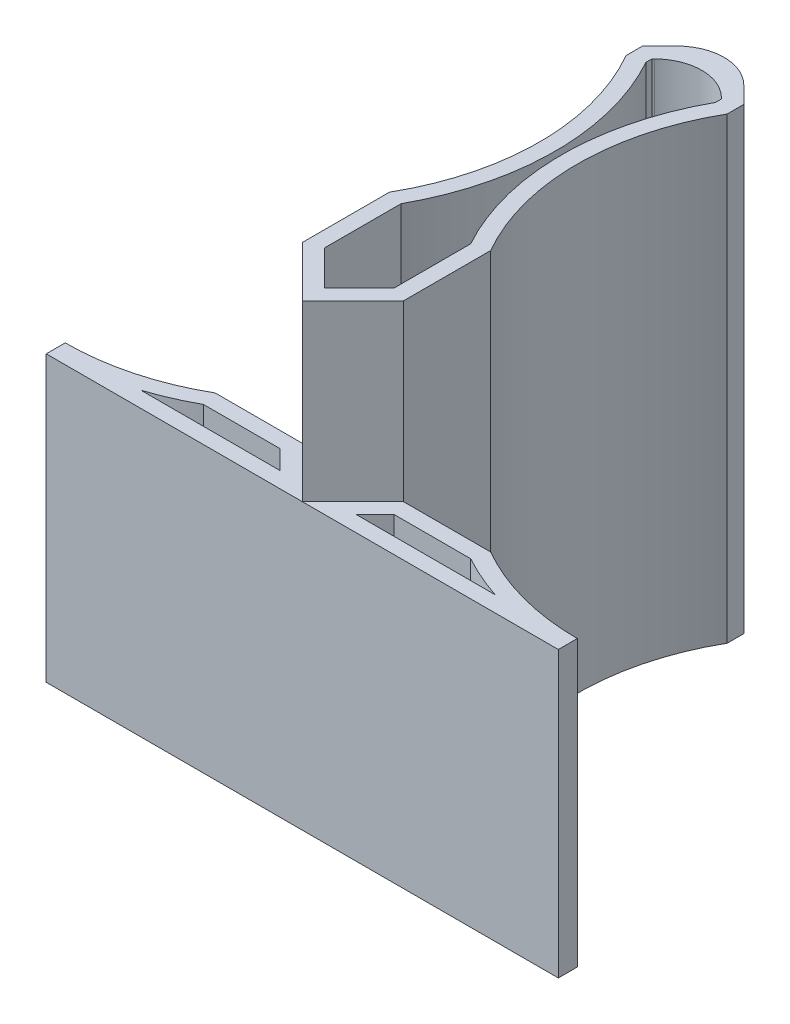
SolidWorks part; units mm, degrees
ref_plane "Front Plane" through (0, 0, 0) normal (0, 0, 1) x (1, 0, 0)
ref_plane "Top Plane" through (0, 0, 0) normal (0, 1, 0) x (1, 0, 0)
ref_plane "Right Plane" through (0, 0, 0) normal (1, 0, 0) x (0, 0, -1)
sketch "Sketch1" plane through (0, 0, 0) normal (0, 1, 0) x (1, 0, 0)
  line L0 (23.7595, 41.275) -> (41.275, 41.275) construction
  line L1 (-41.275, -41.275) -> (-23.7595, -41.275) construction
  line L2 (-41.275, -41.275) -> (-41.275, -23.7595) construction
  line L3 (-41.275, 41.275) -> (-23.7595, 41.275) construction
  line L4 (41.275, -41.275) -> (41.275, -23.7595) construction
  line L5 (-41.275, -41.275) -> (41.275, 41.275) construction
  line L6 (-41.275, 41.275) -> (41.275, -41.275) construction
  line L7 (41.275, 23.7595) -> (41.275, 41.275) construction
  line L8 (-41.275, 23.7595) -> (-41.275, 41.275) construction
  line L9 (23.7595, -41.275) -> (41.275, -41.275) construction
  line L10 (24.7569, 45.085) -> (45.085, 45.085) construction
  line L11 (45.085, 24.7569) -> (45.085, 45.085) construction
  line L12 (45.085, -45.085) -> (45.085, -24.7569) construction
  line L13 (24.7569, -45.085) -> (45.085, -45.085) construction
  line L14 (-45.085, -45.085) -> (-24.7569, -45.085) construction
  line L15 (-45.085, -45.085) -> (-45.085, -24.7569) construction
  line L16 (-45.085, 24.7569) -> (-45.085, 45.085) construction
  line L17 (-45.085, 45.085) -> (-24.7569, 45.085) construction
  line L19 (-51.435, -51.435) -> (51.435, -51.435) construction
  line L20 (-51.435, -51.435) -> (-51.435, 51.435) construction
  line L21 (-51.435, 51.435) -> (51.435, 51.435) construction
  line L22 (51.435, -51.435) -> (51.435, 51.435) construction
  line L23 (-51.435, -51.435) -> (51.435, 51.435) construction
  line L24 (-51.435, 51.435) -> (51.435, -51.435) construction
  arc A1 (-41.275, 23.7595) -> (-41.275, -23.7595) centre (0, 0) ccw construction
  arc A2 (23.7595, 41.275) -> (-23.7595, 41.275) centre (0, 0) ccw construction
  arc A3 (-23.7595, -41.275) -> (23.7595, -41.275) centre (0, 0) ccw construction
  arc A4 (41.275, -23.7595) -> (41.275, 23.7595) centre (0, 0) ccw construction
  arc A5 (45.085, -24.7569) -> (45.085, 24.7569) centre (0, 0) ccw construction
  arc A6 (-24.7569, -45.085) -> (24.7569, -45.085) centre (0, 0) ccw construction
  arc A7 (-45.085, 24.7569) -> (-45.085, -24.7569) centre (0, 0) ccw construction
  arc A8 (24.7569, 45.085) -> (-24.7569, 45.085) centre (0, 0) ccw construction
  point P0 (0, 0)
  dimension "D1" = 82.55
  dimension "D2" = 82.55
  dimension "D3" = 95.25
  dimension "D4" = 3.81
sketch "Sketch2" plane through (0, 0, 0) normal (0, 0, 1) x (1, 0, 0)
  line L0 (0, 48) -> (0, 0) construction
  line L1 (0, 0) -> (0, -9.15) construction
  line L2 (0, 48) -> (0, 82.925) construction
  dimension "Cage height" = 48
  dimension "Plate height" = 34.925
  dimension "D1" = 57.15
  dimension "D2" = 9.15
sketch "Sketch13" plane through (0, 0, 0) normal (0, 1, 0) x (1, 0, 0)
  line L0 (-51.435, -51.435) -> (51.435, -51.435) construction
  line L1 (-41.275, -41.275) -> (-23.7595, -41.275) construction
  line L2 (-41.275, -41.275) -> (-41.275, -23.7595) construction
  line L4 (-51.435, -51.435) -> (0, -51.435)
  line L5 (-41.275, -41.275) -> (-23.7595, -41.275)
  line L6 (-41.275, -41.275) -> (-41.275, -23.7595)
  line L9 (0, -47.625) -> (0, -51.435)
  line L10 (-51.435, 51.435) -> (51.435, -51.435) construction
  line L11 (-41.275, 23.7595) -> (-41.275, 41.275) construction
  line L12 (-51.435, -51.435) -> (-51.435, 51.435) construction
  line L13 (-51.435, 51.435) -> (-41.275, 41.275)
  line L14 (-41.275, 23.7595) -> (-41.275, 41.275)
  line L15 (-51.435, -51.435) -> (-51.435, 51.435)
  arc A0 (-23.7595, -41.275) -> (23.7595, -41.275) centre (0, 0) ccw construction
  arc A2 (-23.7595, -41.275) -> (0, -47.625) centre (0, 0) ccw
  arc A4 (-41.275, 23.7595) -> (-41.275, -23.7595) centre (0, 0) ccw construction
  arc A5 (-41.275, 23.7595) -> (-41.275, -23.7595) centre (0, 0) ccw
extrude "Boss-Extrude2" add sketch "Sketch13" along normal up to vertex (82.925 mm away) and the other way up to vertex (9.15 mm away) up to point (0, 82.925, 0) other way up to point (0, -9.15, 0)
sketch "Sketch15" plane through (0, 82.925, 0) normal (0, 1, 0) x (1, 0, 0)
  line L0 (0, 0) -> (-51.435, -51.435)
  line L1 (-51.435, -51.435) -> (0, -51.435)
  line L2 (0, -51.435) -> (0, 0)
  line L3 (-51.435, -51.435) -> (51.435, -51.435) construction
extrude "Cut-Extrude2" cut sketch "Sketch15" against normal up to vertex (34.925 mm away) up to point (0, 48, 0)
mirror "Mirror1" about plane through (-51.435, 82.925, 51.435) normal (1, 0, 0) of "Boss-Extrude2", "Cut-Extrude2"
sketch "Sketch16" plane through (0, -9.15, 0) normal (0, -1, 0) x (1, 0, 0)
  line L1 (-51.435, -51.435) -> (51.435, -51.435) construction
  circle A5 centre (-51.435, -13.335) radius 1.35
  dimension "D1" = 2.7
  dimension "D2" = 38.1
extrude "Cut-Extrude3" cut sketch "Sketch16" against normal blind 31.75
sketch "Sketch17" plane through (0, 82.925, 0) normal (0, 1, 0) x (1, 0, 0)
  line L0 (7.0944, 7.0944) -> (-7.0944, -7.0944)
  line L1 (7.0944, 7.0944) -> (-44.3406, 58.5294)
  line L2 (-7.0944, -7.0944) -> (-51.435, 37.2462)
  line L3 (-44.3406, 58.5294) -> (-51.435, 51.435)
  line L4 (-41.275, -41.275) -> (41.275, 41.275) construction
  line L5 (-61.595, 41.275) -> (-51.435, 51.435) construction
  line L6 (-51.435, -51.435) -> (-51.435, 51.435) construction
  line L7 (-51.435, 7.7321) -> (-51.435, 82.5591) construction
  line L8 (-95.7756, -7.0944) -> (-51.435, 37.2462)
  line L9 (-58.5294, 58.5294) -> (-51.435, 51.435)
  line L10 (-109.9644, 7.0944) -> (-58.5294, 58.5294)
  line L11 (-109.9644, 7.0944) -> (-95.7756, -7.0944)
  dimension "D1" = 20.066
extrude "Cut-Extrude4" cut sketch "Sketch17" against normal through all
sketch "Sketch18" plane through (0, 82.925, 0) normal (0, 1, 0) x (1, 0, 0)
  line L19 (-58.42, -24.5934) -> (-58.42, -39.9599)
  line L20 (-58.42, -39.9599) -> (-51.435, -46.9449)
  line L21 (-51.435, -46.9449) -> (-44.45, -39.9599)
  line L22 (-44.45, -39.9599) -> (-44.45, -24.5934)
  line L27 (-58.42, -24.5934) -> (-58.42, -39.9599)
  line L28 (-58.42, -39.9599) -> (-51.435, -46.9449)
  line L29 (-51.435, -46.9449) -> (-44.45, -39.9599)
  line L30 (-44.45, -39.9599) -> (-44.45, -24.5934)
  line L32 (-62.9101, -44.45) -> (-78.2766, -44.45)
  line L33 (-87.0077, -48.26) -> (-59.1001, -48.26)
  line L34 (-59.1001, -48.26) -> (-62.9101, -44.45)
  line L35 (-62.9101, -44.45) -> (-78.2766, -44.45)
  line L36 (-87.0077, -48.26) -> (-59.1001, -48.26)
  line L37 (-59.1001, -48.26) -> (-62.9101, -44.45)
  line L42 (-24.5934, -44.45) -> (-39.9599, -44.45)
  line L43 (-39.9599, -44.45) -> (-43.7699, -48.26)
  line L44 (-43.7699, -48.26) -> (-15.8623, -48.26)
  line L45 (-24.5934, -44.45) -> (-39.9599, -44.45)
  line L46 (-39.9599, -44.45) -> (-43.7699, -48.26)
  line L47 (-43.7699, -48.26) -> (-15.8623, -48.26)
  line L48 (-44.45, 25.7711) -> (-51.435, 32.7561)
  line L49 (-44.45, 25.7711) -> (-51.435, 32.7561)
  line L50 (-51.435, 32.7561) -> (-58.42, 25.7711)
  line L51 (-51.435, 32.7561) -> (-58.42, 25.7711)
  line L52 (-58.42, 25.7711) -> (-58.42, 24.5934)
  line L53 (-58.42, 25.7711) -> (-58.42, 24.5934)
  line L54 (-44.45, 24.5934) -> (-44.45, 25.7711)
  line L55 (-44.45, 24.5934) -> (-44.45, 25.7711)
  arc A5 (-87.0077, -48.26) -> (-78.2766, -44.45) centre (-102.87, 0) ccw
  arc A7 (-58.42, -24.5934) -> (-58.42, 24.5934) centre (-102.87, 0) ccw
  arc A8 (-44.45, 24.5934) -> (-44.45, -24.5934) centre (0, 0) ccw
  arc A10 (-58.42, -24.5934) -> (-58.42, 24.5934) centre (-102.87, 0) ccw
  arc A11 (-44.45, 24.5934) -> (-44.45, -24.5934) centre (0, 0) ccw
  arc A12 (-87.0077, -48.26) -> (-78.2766, -44.45) centre (-102.87, 0) ccw
  arc A14 (-24.5934, -44.45) -> (-15.8623, -48.26) centre (0, 0) ccw
  arc A15 (-24.5934, -44.45) -> (-15.8623, -48.26) centre (0, 0) ccw
  dimension "D1" = 3.175
  dimension "D2" = 3.175
  dimension "D3" = 3.175
extrude "Cut-Extrude5" cut sketch "Sketch18" against normal up to surface (60.325 mm away) contours A11 L55 L49 L51 L53 A10 L27 L28 L29 L30 region at (-51.435, 82.925, 12.1349) up to face at (-51.435, 22.6, -14.685)
sketch "Sketch22" plane through (0, 0, 0) normal (0, 1, 0) x (1, 0, 0)
  line L0 (-51.435, -51.435) -> (-51.435, 51.435) construction
  line L1 (-51.435, 51.435) -> (51.435, 51.435) construction
  circle A0 centre (-51.435, -12.065) radius 1.85
  dimension "D1" = 3.7
  dimension "D2" = 63.5
extrude "Cut-Extrude7" cut sketch "Sketch22" against normal through all both and the other way through all
sketch "Sketch20" plane through (0, 22.6, 0) normal (0, 1, 0) x (1, 0, 0)
  line L7 (-56.039, 19.685) -> (-46.831, 19.685)
  line L9 (-47.3448, -18.415) -> (-55.5252, -18.415)
  line L24 (-44.45, 24.5934) -> (-44.45, 25.7711)
  line L25 (-44.45, 25.7711) -> (-51.435, 32.7561)
  line L26 (-51.435, 32.7561) -> (-58.42, 25.7711)
  line L27 (-58.42, 25.7711) -> (-58.42, 24.5934)
  line L28 (-58.42, -24.5934) -> (-58.42, -39.9599)
  line L29 (-58.42, -39.9599) -> (-51.435, -46.9449)
  line L30 (-51.435, -46.9449) -> (-44.45, -39.9599)
  line L31 (-44.45, -39.9599) -> (-44.45, -24.5934)
  line L32 (-44.45, 24.5934) -> (-44.45, 25.7711)
  line L33 (-44.45, 25.7711) -> (-51.435, 32.7561)
  line L34 (-51.435, 32.7561) -> (-58.42, 25.7711)
  line L35 (-58.42, 25.7711) -> (-58.42, 24.5934)
  line L36 (-58.42, -24.5934) -> (-58.42, -39.9599)
  line L37 (-58.42, -39.9599) -> (-51.435, -46.9449)
  line L38 (-51.435, -46.9449) -> (-44.45, -39.9599)
  line L39 (-44.45, -39.9599) -> (-44.45, -24.5934)
  arc A0 (-58.42, -24.5934) -> (-58.42, 24.5934) centre (-102.87, 0) ccw construction
  arc A1 (-47.3448, -18.415) -> (-44.45, -24.5934) centre (0, 0) ccw
  arc A5 (-58.42, -24.5934) -> (-58.42, 24.5934) centre (-102.87, 0) ccw construction
  arc A9 (-44.45, 24.5934) -> (-44.45, -24.5934) centre (0, 0) ccw construction
  arc A11 (-44.45, 24.5934) -> (-44.45, -24.5934) centre (0, 0) ccw construction
  arc A13 (-58.42, -24.5934) -> (-58.42, 24.5934) centre (-102.87, 0) ccw
  arc A14 (-44.45, 24.5934) -> (-44.45, -24.5934) centre (0, 0) ccw
  arc A15 (-58.42, -24.5934) -> (-55.5252, -18.415) centre (-102.87, 0) ccw
  arc A16 (-44.45, 24.5934) -> (-46.831, 19.685) centre (0, 0) ccw
  arc A18 (-56.039, 19.685) -> (-58.42, 24.5934) centre (-102.87, 0) ccw
  circle A19 centre (-51.435, 13.335) radius 1.35 construction
  circle A20 centre (-51.435, -12.065) radius 1.85 construction
  dimension "D2" = 6.35
  dimension "D5" = 6.35
  dimension "D1" = 0
extrude "Cut-Extrude9" cut sketch "Sketch18<3>" against normal through all contours L36 L37 L35 A12 | L45 L46 L47 A15
sketch "Sketch18<3>" plane through (0, 82.925, 0) normal (0, 1, 0) x (1, 0, 0) same geometry as "Sketch18"
extrude "Cut-Extrude10" cut sketch "Sketch20" against normal through all
fillet "Fillet2" radius 9.525 2 edges at (-51.435, 36.8875, -37.2462) (-51.435, 36.8875, -32.7561)
equation "\"tightTol\"= 0.005in"
equation "\"normTol\"= 0.01in"
equation "\"looseTol\"= 0.02in"
equation "\"Cage height@Sketch2\"=48mm"
equation "\"Plate height@Sketch2\"=1.375"
equation "\"D1@Sketch17\"=0.75in+2*\"looseTol\""
equation "\"D1@Sketch22\"=3.7mm"
equation "\"D1@Sketch16\"=2.7mm"
